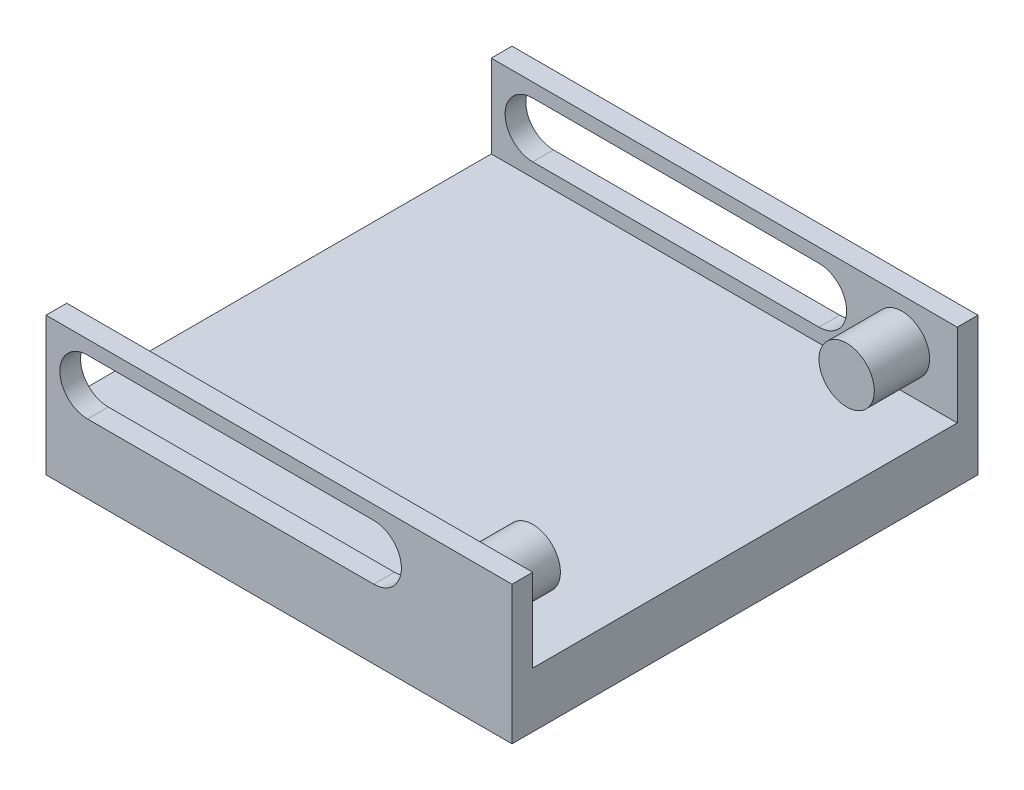
SolidWorks part; units mm, degrees
ref_plane "Front Plane" through (0, 0, 0) normal (0, 0, 1) x (1, 0, 0)
ref_plane "Top Plane" through (0, 0, 0) normal (0, 1, 0) x (1, 0, 0)
ref_plane "Right Plane" through (0, 0, 0) normal (1, 0, 0) x (0, 0, -1)
sketch "Sketch1" plane through (0, 0, 0) normal (0, 1, 0) x (1, 0, 0)
  line L0 (-33.7032, -32.2032) -> (0, -32.2032)
  line L1 (0, 0) -> (-33.7032, 0)
  line L2 (0, 0) -> (0, -33.7032)
  line L3 (0, -33.7032) -> (-33.7032, -33.7032)
  line L4 (-33.7032, 0) -> (-33.7032, -33.7032)
  line L5 (-33.7032, -1.5) -> (0, -1.5)
  dimension "D1" = 1.5
  dimension "D2" = 1.5
extrude "Boss-Extrude1" add sketch "Sketch1" along normal blind 4 contours L5 L4 L0 L2 region at (-16.8516, 0, 16.8516)
extrude "Boss-Extrude2" add sketch "Sketch1<3>" along normal blind 10 contours L0 L4 L3 L2 | L4 L5 L2 L1 region at (-16.8516, 0, 32.9532) region at (-16.8516, 0, 0.75)
sketch "Sketch1<3>" plane through (0, 0, 0) normal (0, 1, 0) x (1, 0, 0) same geometry as "Sketch1"
sketch "Sketch4" plane through (0, 0, 1.5) normal (0, 0, 1) x (1, 0, 0)
  line L0 (-4, 10) -> (-4, 4)
  line L1 (-33.7032, 10) -> (0, 10) construction
  line L2 (-33.7032, 4) -> (0, 4) construction
  circle A0 centre (-4, 7) radius 2
  dimension "D1" = 4
sketch "Sketch5" plane through (0, 0, 32.2032) normal (0, 0, -1) x (-1, 0, 0)
  line L0 (4, 10) -> (4, 4)
  line L1 (33.7032, 10) -> (0, 10) construction
  line L2 (33.7032, 4) -> (0, 4) construction
  circle A0 centre (4, 7) radius 2
  dimension "D1" = 4
extrude "Boss-Extrude3" add sketch "Sketch5" along normal blind 4 contours L0 A0 | L0 A0 region at (-4.8488, 7, 32.2032) region at (-3.1512, 7, 32.2032)
extrude "Boss-Extrude4" add sketch "Sketch4" along normal blind 4 contours A0
sketch "Sketch11" plane through (0, 0, 32.2032) normal (0, 0, -1) x (-1, 0, 0)
  line L0 (30.7032, 10) -> (30.7032, 4)
  line L1 (33.7032, 10) -> (0, 10) construction
  line L2 (33.7032, 4) -> (0, 4) construction
  line L4 (30.7032, 9) -> (10, 9)
  line L5 (30.7032, 9) -> (30.7032, 5)
  line L6 (30.7032, 5) -> (10, 5)
  line L7 (10, 9) -> (10, 5)
  arc A0 (30.7032, 5) -> (30.7032, 9) centre (30.7032, 7) ccw
  arc A1 (10, 9) -> (10, 5) centre (10, 7) ccw
  dimension "D1" = 3
extrude "Cut-Extrude1" cut sketch "Sketch11" along normal blind 38 and the other way blind 10 contours L7 A1 | L4 L7 L6 L0 | L0 A0 region at (-31.5521, 7, 32.2032) region at (-20.3516, 7, 32.2032) region at (-9.1512, 7, 32.2032)
